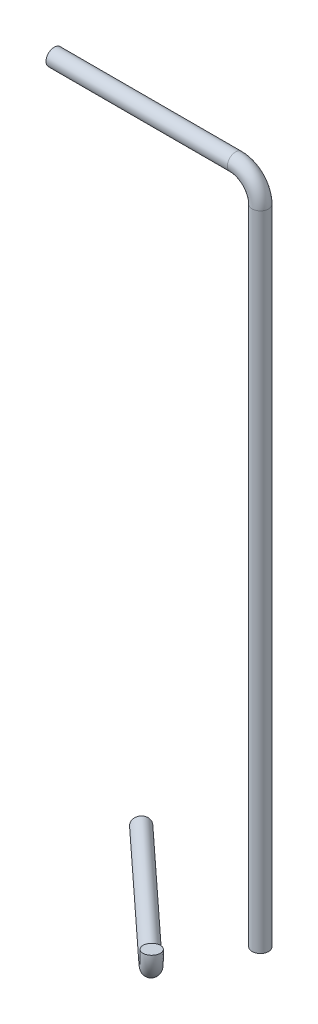
SolidWorks part; units mm, degrees
ref_plane "Front Plane" through (0, 0, 0) normal (0, 0, 1) x (1, 0, 0)
ref_plane "Top Plane" through (0, 0, 0) normal (0, 1, 0) x (1, 0, 0)
ref_plane "Right Plane" through (0, 0, 0) normal (1, 0, 0) x (0, 0, -1)
sketch "Sketch1" plane through (0, 0, 0) normal (0, 0, 1) x (1, 0, 0)
  line L0 (0, 0) -> (22, 0)
  line L1 (25, -3) -> (25, -81.02)
  arc A0 (22, 0) -> (25, -3) centre (22, -3) cw
  point P6 (25, 0)
  dimension "D3" = 3
  dimension "D1" = 25
  dimension "D2" = 81.02
sketch "Sketch3" plane through (0, 0, 0) normal (1, 0, 0) x (0, 0, -1)
  circle A0 centre (0, 0) radius 1
  dimension "D1" = 2
sweep "Sweep1" add profiles "Sketch3" path "Sketch1"
ref_plane "Plane2" through (7.0545, 0, -7.6327) normal (0.6787, 0, -0.7344) x (-0.7344, 0, -0.6787)
ref_axis "Axis1" through (0, 0, 0) along (1, 0, 0)
ref_plane "Plane3" through (5.1879, 0, -5.6132) normal (0.6787, 0, -0.7344) x (-0.7344, 0, -0.6787)
sketch "Sketch4" plane through (5.1879, 0, -5.6132) normal (0.6787, 0, -0.7344) x (-0.7344, 0, -0.6787)
  line L4 (-15.3684, -84.2524) -> (4.6316, -84.2524)
  line L6 (-19.3594, -81.02) -> (-17.3594, -81.02) construction
  arc A0 (-18.3594, -81.02) -> (-15.3684, -84.2524) centre (-15.3684, -81.2524) ccw
  dimension "D2" = 20
  dimension "D1" = 3
ref_plane "Plane5" through (1.7866, -84.2524, -8.7568) normal (-0.7344, 0, -0.6787) x (-0.6787, 0, 0.7344)
sketch "Sketch6" plane through (1.7866, -84.2524, -8.7568) normal (-0.7344, 0, -0.6787) x (-0.6787, 0, 0.7344)
  line L0 (0, 3.2324) -> (0, 0) construction
  circle A0 centre (0, 0) radius 1
  dimension "D1" = 2
sweep "Sweep3" add profiles "Sketch6" path "Sketch4"
